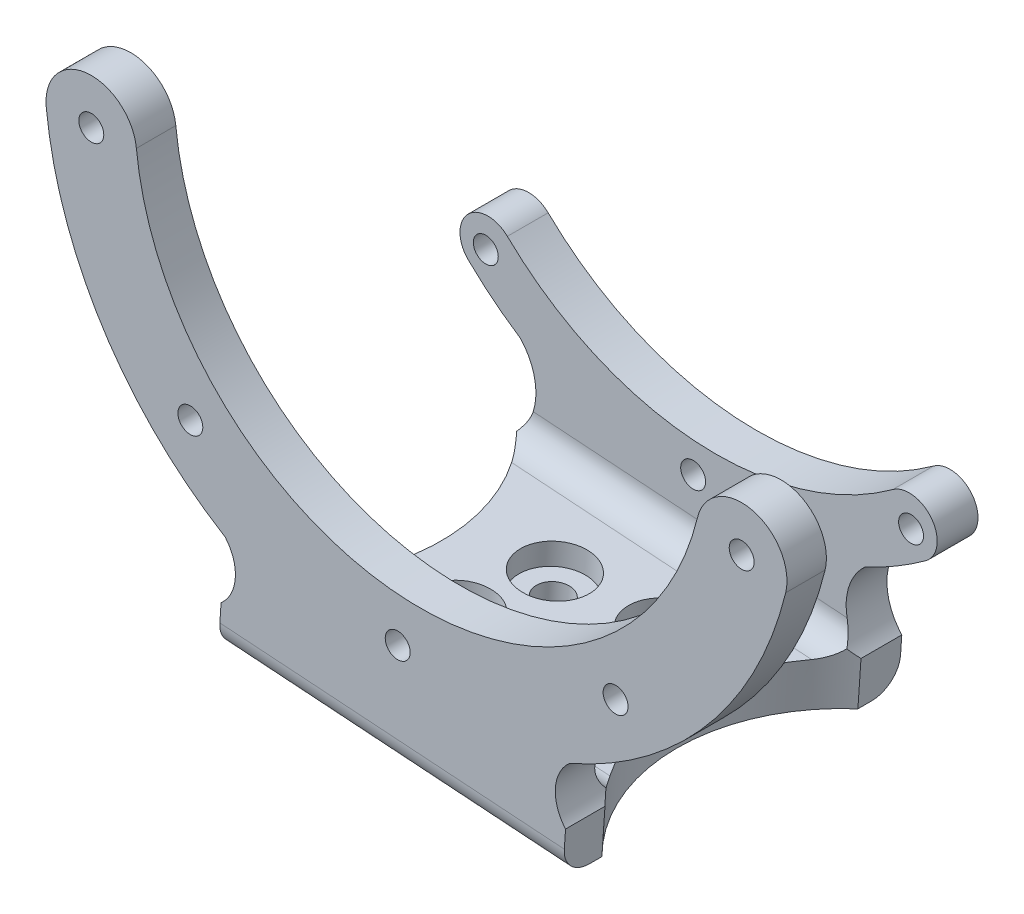
SolidWorks part; units mm, degrees
ref_plane "前视基准面" through (0, 0, 0) normal (0, 0, 1) x (1, 0, 0)
ref_plane "上视基准面" through (0, 0, 0) normal (0, 1, 0) x (1, 0, 0)
ref_plane "右视基准面" through (0, 0, 0) normal (1, 0, 0) x (0, 0, -1)
other "Configuration Table"
sketch "草图1" plane through (0, 0, 0) normal (0, 0, 1) x (1, 0, 0)
  line L4 (-80.824, -6.6077) -> (-34.0117, -9.8356)
  line L6 (-79.85, 7.518) -> (-80.824, -6.6077)
  line L7 (-33.0377, 4.2892) -> (-34.0117, -9.8356)
  arc A0 (-95.3694, 35.7956) -> (-79.85, 7.518) centre (-54.0884, 40.0539) ccw
  arc A1 (-85.4221, 36.8217) -> (-23.4939, 32.5556) centre (-54.0884, 40.0539) ccw
  arc A2 (-95.3694, 35.7956) -> (-85.4221, 36.8217) centre (-90.3958, 36.3086) cw
  arc A3 (-23.4939, 32.5556) -> (-13.7813, 30.1752) centre (-18.6376, 31.3654) cw
  arc A4 (-82.9451, 10.2287) -> (-75.9917, 17.4155) centre (-79.4684, 13.8221) cw
  arc A5 (-29.5973, 6.5512) -> (-35.4987, 14.6242) centre (-32.548, 10.5877) ccw
  arc A6 (-33.0377, 4.2892) -> (-13.7813, 30.1752) centre (-54.0884, 40.0539) ccw
  point P20 (-57.4178, -8.2217)
sketch "草图2" plane through (0, 0, 0) normal (0, 0, 1) x (1, 0, 0)
  circle A0 centre (-90.3958, 36.3086) radius 1.375
  circle A1 centre (-79.4684, 13.8221) radius 1.375
  circle A2 centre (-56.5917, 3.7499) radius 1.375
  circle A3 centre (-32.548, 10.5877) radius 1.375
  circle A4 centre (-18.6376, 31.3654) radius 1.375
extrude "凸台-拉伸2" add sketch "草图1" along normal blind 37.1 contours L7 A6 A5 A1 A4 A0 L6 L4 | A5 A6 A3 A1 | A0 A4 A1 A2 region at (-56.6587, 2.7798, 0) region at (-87.9346, 27.8841, 0) region at (-22.2317, 23.3565, 0)
extrude "切除-拉伸2" cut sketch "草图2" along normal blind 37.1
sketch "草图7" plane through (-33.1757, 2.2876, 0) normal (0.9976, -0.0688, 0) x (0, 0, -1)
  line L0 (-32.75, -7.1519) -> (-32.75, 48.4933)
  line L5 (-4.5, -7.1519) -> (-4.5, 48.4933)
  line L6 (-4.5, 48.4933) -> (-32.75, 48.4933)
  line L7 (-32.75, -7.1519) -> (-4.5, -7.1519)
extrude "切除-拉伸3" cut sketch "草图7" against normal blind 66.1 and the other way blind 43
sketch "草图8" plane through (0, 0, 0) normal (0, 0, -1) x (-1, 0, 0)
  arc A0 (82.9451, 10.2287) -> (29.5973, 6.5512) centre (54.0884, 40.0539) ccw
  arc A1 (75.9917, 17.4155) -> (35.4987, 14.6242) centre (54.0884, 40.0539) ccw
  arc A2 (29.5973, 6.5512) -> (35.4987, 14.6242) centre (32.548, 10.5877) cw
  arc A3 (75.9917, 17.4155) -> (82.9451, 10.2287) centre (79.4684, 13.8221) cw
extrude "切除-拉伸4" cut sketch "草图8" against normal blind 20.1
sketch "草图9" plane through (0, 0, 37.1) normal (0, 0, 1) x (1, 0, 0)
  line L0 (-38.4141, -9.532) -> (-34.0117, -9.8356)
  line L1 (-82.9451, 10.2287) -> (-75.9917, 17.4155)
  line L2 (-79.85, 7.518) -> (-80.824, -6.6077)
  line L3 (-29.5973, 6.5512) -> (-35.4987, 14.6242)
  line L4 (-79.4684, 13.8221) -> (-56.5917, 3.7499)
  line L5 (-56.5917, 3.7499) -> (-32.548, 10.5877)
  line L6 (-68.03, 8.786) -> (-68.803, -2.4247)
  line L8 (-44.5698, 7.1688) -> (-45.3429, -4.0424)
  line L12 (-38.0702, -4.5439) -> (-38.4141, -9.532)
  line L16 (-80.824, -6.6077) -> (-76.4202, -6.9114)
  line L20 (-76.0763, -1.9232) -> (-38.0702, -4.5439)
  line L23 (-34.0117, -9.8356) -> (-33.0377, 4.2892)
  line L26 (-76.0763, -1.9232) -> (-76.4202, -6.9114)
  arc A0 (-79.85, 7.518) -> (-75.6277, 4.5813) centre (-54.0884, 40.0539) ccw
  arc A1 (-85.4221, 36.8217) -> (-23.4939, 32.5556) centre (-54.0884, 40.0539) ccw
  arc A2 (-95.3694, 35.7956) -> (-85.4221, 36.8217) centre (-90.2948, 35.3298) cw
  arc A3 (-75.6277, 4.5813) -> (-76.0763, -1.9232) centre (-79.1043, 1.5533) cw
  arc A4 (-23.4939, 32.5556) -> (-13.7813, 30.1752) centre (-18.6376, 31.3654) cw
  arc A5 (-38.0702, -4.5439) -> (-37.6217, 1.9607) centre (-34.5937, -1.5158) cw
  arc A6 (-37.6217, 1.9607) -> (-33.0377, 4.2892) centre (-54.0884, 40.0539) ccw
  arc A7 (-29.5973, 6.5512) -> (-13.7813, 30.1752) centre (-54.0884, 40.0539) ccw
  point P46 (-72.8285, 4.3883)
  line M13 (-34.0117, -9.8356) -> (-33.0377, 4.2892)
  line M19 (-79.85, 7.518) -> (-80.824, -6.6077)
  line M20 (-80.824, -6.6077) -> (-34.0117, -9.8356)
extrude "切除-拉伸5" cut sketch "草图9" against normal blind 51.1 contours A3 A0 L26 M19 M20 | A6 A5 L12 M20 M13 region at (-35.9581, -3.0949, 37.1) region at (-77.9702, -0.1978, 37.1)
sketch "草图11" plane through (-0.492, -7.135, 0) normal (0.0688, 0.9976, 0) x (0.9976, -0.0688, 0)
  line L0 (-75.7637, -4.5) -> (-69.8137, -4.5)
  line L1 (-37.6674, -4.5) -> (-75.7637, -4.5) construction
  line L2 (-37.6674, -4.5) -> (-43.6174, -4.5)
  line L3 (-75.7637, -32.75) -> (-69.8137, -32.75)
  line L4 (-37.6674, -32.75) -> (-75.7637, -32.75) construction
  line L5 (-37.6674, -32.75) -> (-43.6174, -32.75)
  line L6 (-25.6777, -32.75) -> (-87.7528, -32.75) construction
  line L7 (-69.8137, -4.5) -> (-69.8137, -7.4)
  line L8 (-69.8137, -32.75) -> (-69.8137, -29.85)
  line L9 (-43.6174, -4.5) -> (-43.6174, -7.4)
  line L10 (-43.6174, -32.75) -> (-43.6174, -29.85)
  line L11 (-56.7156, -18.625) -> (-59.9009, -15.8952)
  line L12 (-56.7156, -18.625) -> (-52.0648, -14.6393)
  line L14 (-56.7156, -18.625) -> (-53.5303, -21.3548)
  line L19 (-62.7788, -23.8089) -> (-62.8113, -23.8367)
  line L22 (-62.7788, -23.8089) -> (-62.7821, -23.8299)
  line L23 (-56.7156, -18.625) -> (-61.3862, -22.6183)
  circle A0 centre (-61.3246, -14.6751) radius 1.875
  circle A1 centre (-62.8113, -23.8367) radius 1.875
  circle A2 centre (-50.6411, -13.4192) radius 1.875
  circle A3 centre (-52.1066, -22.5749) radius 1.875
sketch "草图14" plane through (-0.492, -7.135, 0) normal (0.0688, 0.9976, 0) x (0.9976, -0.0688, 0)
  circle A0 centre (-61.3246, -14.6751) radius 3.8
  circle A1 centre (-50.6411, -13.4192) radius 3.8
  circle A2 centre (-52.1066, -22.5749) radius 3.8
  circle A3 centre (-62.8113, -23.8367) radius 3.8
extrude "切除-拉伸11" cut sketch "草图11" against normal blind 11 contours A0 | A2 | A3 | A1 region at (-61.6713, -2.9165, 14.6751) region at (-51.0131, -3.6514, 13.4192) region at (-52.4751, -3.5506, 22.5749) region at (-61.4494, -2.9318, 23.2057)
extrude "切除-拉伸12" cut sketch "草图14" against normal blind 2.5
sketch "草图15" plane through (-0.492, -7.135, 0) normal (0.0688, 0.9976, 0) x (0.9976, -0.0688, 0)
  line L0 (-25.6777, -32.75) -> (-87.7528, -32.75) construction
  line L1 (-75.7637, -4.5) -> (-75.7637, -32.75) construction
  line L2 (-75.7637, -4.5) -> (-75.7637, -32.75)
  line L3 (-37.6674, -4.5) -> (-37.6674, -32.75)
  arc A0 (-75.7637, -4.5) -> (-75.7637, -32.75) centre (-89.8887, -18.625) cw
  arc A1 (-37.6674, -4.5) -> (-37.6674, -32.75) centre (-23.5424, -18.625) ccw
extrude "切除-拉伸13" cut sketch "草图15" against normal blind 10
sketch "草图16" plane through (0, 0, 0) normal (0, 0, -1) x (-1, 0, 0)
  arc A0 (30.9251, 8.3676) -> (37.6217, 4.4252) centre (54.0884, 40.0539) ccw
  arc A1 (34.5663, 13.3486) -> (77.0903, 16.28) centre (54.0884, 40.0539) ccw
  arc A3 (30.9251, 8.3676) -> (34.5663, 13.3486) centre (32.7457, 10.8581) cw
  arc A4 (77.0903, 16.28) -> (81.3805, 11.8458) centre (79.2354, 14.0629) cw
  arc A5 (29.5973, 6.5512) -> (37.6217, 1.9607) centre (54.0884, 40.0539) ccw
  arc A6 (35.4987, 14.6242) -> (75.9917, 17.4155) centre (54.0884, 40.0539) ccw
  arc A7 (29.5973, 6.5512) -> (35.4987, 14.6242) centre (32.548, 10.5877) cw
  arc A8 (75.9917, 17.4155) -> (82.9451, 10.2287) centre (79.4684, 13.8221) cw
  arc A9 (38.0702, -4.5439) -> (37.6217, 1.9607) centre (34.5937, -1.5158) ccw
  arc A10 (76.0763, -1.9232) -> (75.6495, -1.4995) centre (79.1043, 1.5533) cw
  arc A11 (75.6277, 4.5813) -> (82.9451, 10.2287) centre (54.0884, 40.0539) ccw
  arc A12 (37.6217, 4.4252) -> (38.0702, -4.5439) centre (33.3614, -0.2836) cw
  arc A13 (76.0763, -1.9232) -> (75.6182, 7.2358) centre (80.4268, 2.8853) cw
  arc A14 (76.0763, -1.9232) -> (75.6277, 4.5813) centre (79.1043, 1.5533) cw
  arc A15 (75.6182, 7.2358) -> (81.3805, 11.8458) centre (54.0884, 40.0539) ccw
  arc M14 (76.0763, -1.9232) -> (75.6277, 4.5813) centre (79.1043, 1.5533) cw
  arc M15 (75.6277, 4.5813) -> (82.9451, 10.2287) centre (54.0884, 40.0539) ccw
  arc M16 (82.9451, 10.2287) -> (75.9917, 17.4155) centre (79.4684, 13.8221) ccw
  arc M17 (75.9917, 17.4155) -> (35.4987, 14.6242) centre (54.0884, 40.0539) cw
  arc M18 (35.4987, 14.6242) -> (29.5973, 6.5512) centre (32.548, 10.5877) ccw
  arc M19 (29.5973, 6.5512) -> (37.6217, 1.9607) centre (54.0884, 40.0539) ccw
  arc M20 (37.6217, 1.9607) -> (38.0702, -4.5439) centre (34.5937, -1.5158) cw
extrude "切除-拉伸16" cut sketch "草图16" against normal blind 7.9 contours A15 A13 A12 A0 A3 A1 A4 M14 M15 M16 M17 M18 M19 M20 region at (-33.8634, 5.7, 0)
fillet "圆角1" radius 3 1 edges at (-57.0732, -3.2336, 32.75)
fillet "圆角2" radius 3 1 edges at (-57.0732, -3.2336, 4.5)
fillet "圆角3" radius 3 1 edges at (-57.4172, -8.2217, 37.1)
fillet "圆角4" radius 3 1 edges at (-57.4172, -8.2217, 0)
